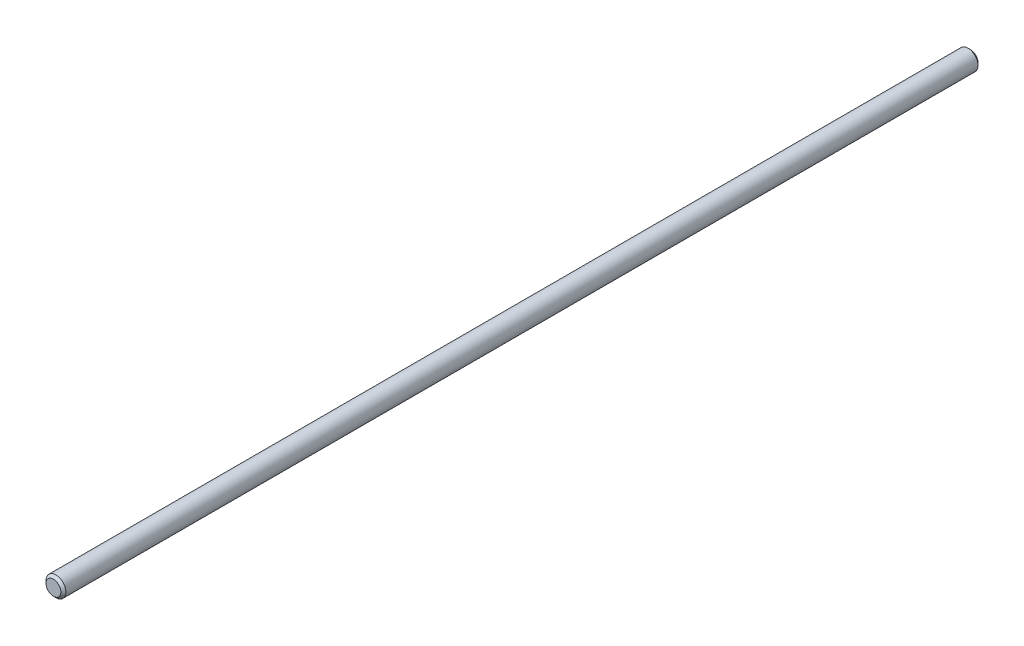
SolidWorks part; units mm, degrees
ref_plane "Front Plane" through (0, 0, 0) normal (0, 0, 1) x (1, 0, 0)
ref_plane "Top Plane" through (0, 0, 0) normal (0, 1, 0) x (1, 0, 0)
ref_plane "Right Plane" through (0, 0, 0) normal (1, 0, 0) x (0, 0, -1)
sketch "Sketch1" plane through (0, 0, 0) normal (0, 0, 1) x (1, 0, 0)
  circle A0 centre (0, 0) radius 4
  dimension "D1" = 8
extrude "Boss-Extrude1" add sketch "Sketch1" along normal blind 370
chamfer "Chamfer1" distance 1 angle 45 2 edges at (4, 0, 370) (4, 0, 0)
